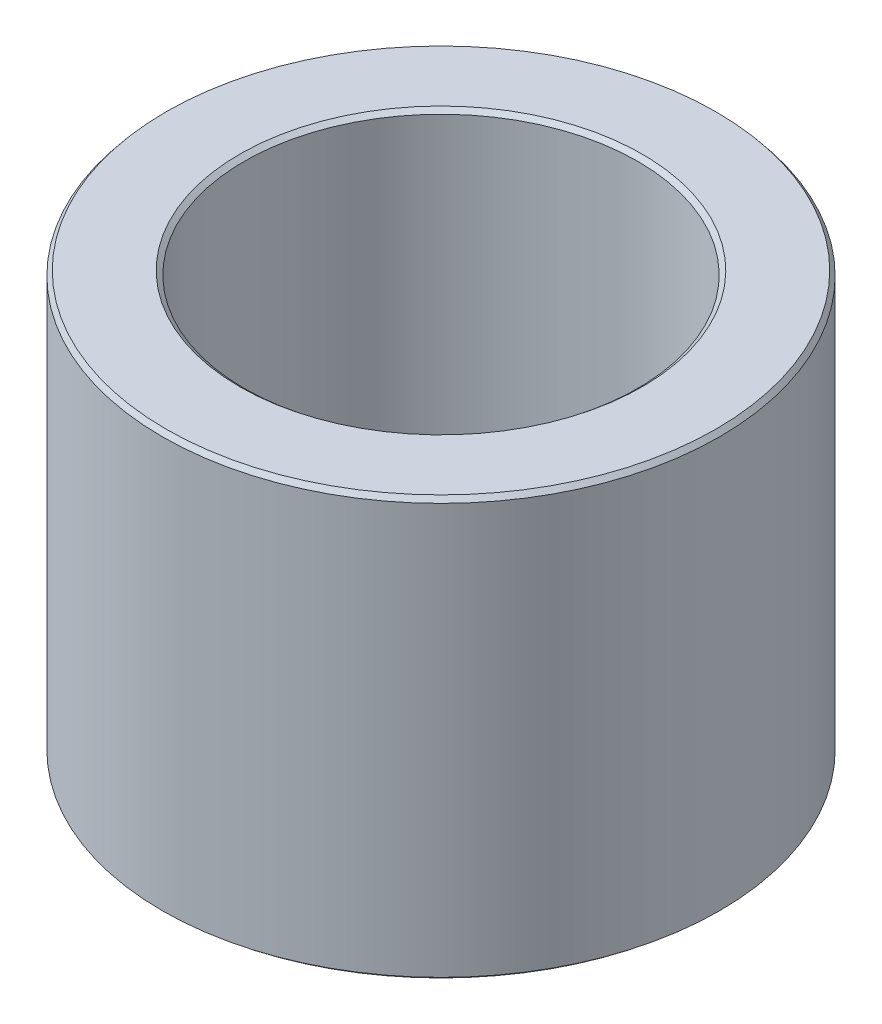
SolidWorks part; units mm, degrees
ref_plane "Front Plane" through (0, 0, 0) normal (0, 0, 1) x (1, 0, 0)
ref_plane "Top Plane" through (0, 0, 0) normal (0, 1, 0) x (1, 0, 0)
ref_plane "Right Plane" through (0, 0, 0) normal (1, 0, 0) x (0, 0, -1)
sketch "Sketch1" plane through (0, 0, 0) normal (0, 1, 0) x (1, 0, 0)
  circle A0 centre (0, 0) radius 55
  dimension "SLEEVE_OD" = 110
extrude "Boss-Extrude1" add sketch "Sketch1" along normal blind 82.6806
sketch "Sketch2" plane through (0, 0, 0) normal (0, 1, 0) x (1, 0, 0)
  circle A0 centre (0, 0) radius 38.8217
  dimension "BORE_D" = 77.6434
extrude "Cut-Extrude1" cut sketch "Sketch2" along normal through all
chamfer "Chamfer1" distance 0.9211 angle 39.267 4 edges at (0, 82.6806, 38.8217) (0, 0, 38.8217) (0, 0, 55) (0, 82.6806, 55) first distance on face at (0, 82.6806, 38.8217) first distance on face at (0, 0, 38.8217) first distance on face at (0, 82.6806, 55)
